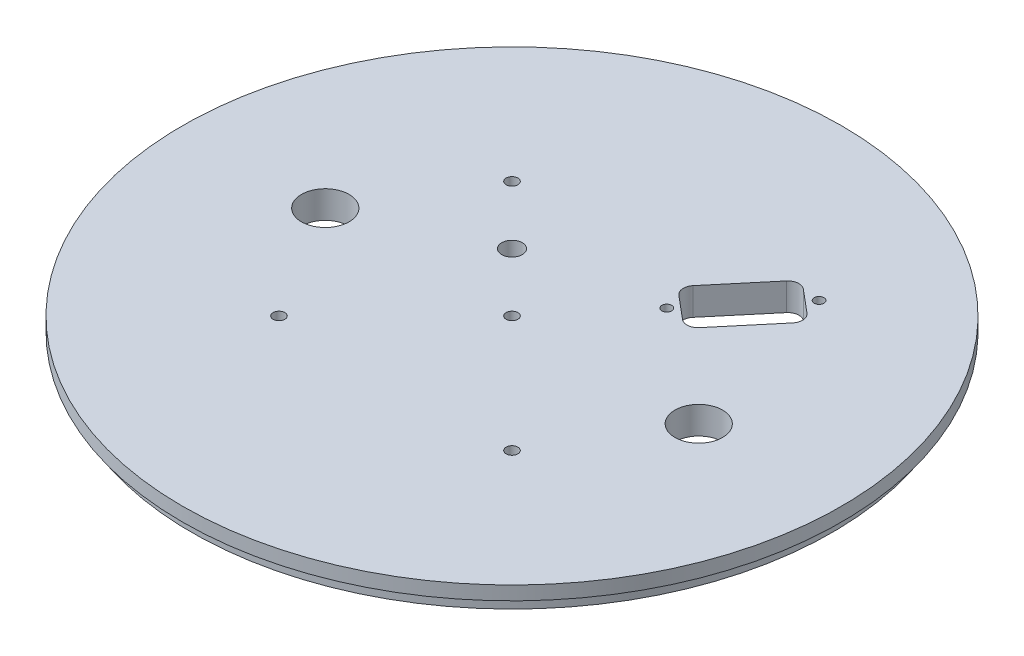
SolidWorks part; units mm, degrees
material "6061-T6 (SS)"
ref_plane "Front Plane" through (0, 0, 0) normal (0, 0, 1) x (1, 0, 0)
ref_plane "Top Plane" through (0, 0, 0) normal (0, 1, 0) x (1, 0, 0)
ref_plane "Right Plane" through (0, 0, 0) normal (1, 0, 0) x (0, 0, -1)
sketch "Sketch1" plane through (0, 0, 0) normal (0, 1, 0) x (1, 0, 0)
  line L0 (0, -76.2) -> (0, 76.2) construction
  line L1 (-76.2, 0) -> (76.2, 0) construction
  line L2 (-26.9408, 26.9408) -> (0, 0) construction
  line L3 (0, 56.7387) -> (0, 29.6936) construction
  line L4 (3.6407, 56.7387) -> (3.6407, 29.6936) construction
  line L5 (-3.6407, 56.7387) -> (-3.6407, 29.6936) construction
  line L6 (0, -56.7387) -> (0, -29.6936) construction
  line L7 (3.6407, -56.7387) -> (3.6407, -29.6936) construction
  line L8 (-3.6407, -56.7387) -> (-3.6407, -29.6936) construction
  line L9 (-53.8815, -53.8815) -> (54.3236, 54.3236) construction
  line L10 (-26.9408, -26.9408) -> (0, 0) construction
  circle A0 centre (0, 0) radius 76.2
  circle A1 centre (0, 0) radius 3.175 construction
  circle A2 centre (43.18, 0) radius 5.5
  circle A3 centre (-43.18, 0) radius 5.5
  circle A4 centre (-26.9408, 26.9408) radius 1.3589
  arc A6 (3.6407, 56.7387) -> (-3.6407, 56.7387) centre (0, 56.7387) ccw construction
  arc A7 (-3.6407, 29.6936) -> (3.6407, 29.6936) centre (0, 29.6936) ccw construction
  arc A8 (3.6407, -56.7387) -> (-3.6407, -56.7387) centre (0, -56.7387) cw construction
  arc A9 (-3.6407, -29.6936) -> (3.6407, -29.6936) centre (0, -29.6936) cw construction
  circle A10 centre (26.9408, -26.9408) radius 1.3589
  circle A11 centre (-13.4704, 13.4704) radius 2.3813
  circle A13 centre (-26.9408, -26.9408) radius 1.3589
  circle A14 centre (0, 0) radius 38.1 construction
  circle A15 centre (0, 0) radius 1.3589
  point P16 (0, 43.2162)
  point P19 (0, 0)
  point P26 (0, -43.2162)
  dimension "D1" = 152.4
  dimension "D2" = 6.35
  dimension "D3" = 11
  dimension "D5" = 2.7178
  dimension "D8" = 4.7625
  dimension "D10" = 2.7178
  dimension "D12" = 2.7178
  dimension "D6" = 38.1
  dimension "D7" = 45
  dimension "D4" = 45
  dimension "D9" = 43.18
  dimension "D11" = 38.1
extrude "Boss-Extrude1" add sketch "Sketch1" along normal blind 6.35
sketch "Sketch2" plane through (0, 0, 0) normal (0, -1, 0) x (1, 0, 0)
  circle A0 centre (0, 0) radius 76.2
  circle A1 centre (0, 0) radius 74.041
  dimension "D1" = 152.4
  dimension "D2" = 148.082
extrude "Cut-Extrude1" cut sketch "Sketch2" against normal blind 3.175
sketch "Sketch3" plane through (0, 6.35, 0) normal (0, 1, 0) x (1, 0, 0)
  line L0 (0, 76.2) -> (0, -76.2) construction
  line L1 (-76.2, 0) -> (76.2, 0) construction
  line L2 (0, 34.798) -> (0, 13.97) construction
  line L3 (3.2385, 34.798) -> (3.2385, 13.97)
  line L4 (-3.2385, 34.798) -> (-3.2385, 13.97)
  line L5 (0, -34.798) -> (0, -13.97) construction
  line L6 (3.2385, -34.798) -> (3.2385, -13.97)
  line L7 (-3.2385, -34.798) -> (-3.2385, -13.97)
  circle A0 centre (0, 0) radius 76.2 construction
  arc A1 (3.2385, 34.798) -> (-3.2385, 34.798) centre (0, 34.798) ccw
  arc A2 (-3.2385, 13.97) -> (3.2385, 13.97) centre (0, 13.97) ccw
  arc A3 (3.2385, -34.798) -> (-3.2385, -34.798) centre (0, -34.798) cw
  arc A4 (-3.2385, -13.97) -> (3.2385, -13.97) centre (0, -13.97) cw
  point P7 (0, 13.97)
  point P8 (0, 34.798)
  point P12 (0, 24.384)
  point P20 (0, -24.384)
  point P25 (0, -34.798)
  point P26 (0, -13.97)
  dimension "D1" = 13.97
  dimension "D2" = 20.828
  dimension "D3" = 6.477
extrude "Cut-Extrude2" cut sketch "Sketch3" against normal blind 3.556 from offset 3.175 offset against normal yes
hole_wizard "Tap Drill for #4-40 Tap1" positions "Sketch5" profile "Sketch6" hole size "#4-40" standard "ANSI Inch" end condition through all
sketch "Sketch5" plane through (0, 6.35, 0) normal (0, 1, 0) x (1, 0, 0)
  line L0 (0, 0) -> (53.6567, 63.9455) construction
  line L2 (0, 0) -> (43.18, 0) construction
  point P0 (16.3268, 19.4575)
  point P2 (32.3965, 38.6086)
  dimension "D1" = 50
  dimension "D2" = 25
  dimension "D3" = 25.4
sketch "Sketch6" plane through (16.3268, 6.35, -19.4575) normal (1, 0, 0) x (0, 0, 1)
  line L0 (0, 0) -> (0, 6.35)
  line L1 (0, 6.35) -> (1.1303, 6.35)
  line L2 (1.1303, 6.35) -> (1.1303, 0)
  line L5 (1.1303, 0) -> (0, 0)
  line L11 (0, -6.35) -> (0, 107.95) construction
  dimension "Thru Hole Dia." = 2.2606
  dimension "Thru Hole Depth" = 6.35
sketch "Sketch4" plane through (0, 6.35, 0) normal (0, 1, 0) x (1, 0, 0)
  line L0 (15.1695, 23.4128) -> (20.423, 19.0046)
  line L1 (14.8564, 26.9913) -> (24.7219, 38.7485)
  line L2 (24.0014, 19.3177) -> (33.8669, 31.0749)
  line L3 (28.3003, 39.0616) -> (33.5538, 34.6533)
  line L4 (0, 0) -> (32.3965, 38.6086) construction
  circle A1 centre (16.3268, 19.4575) radius 1.1303 construction
  arc A2 (24.7219, 38.7485) -> (28.3003, 39.0616) centre (26.6676, 37.1158) cw
  arc A3 (33.8669, 31.0749) -> (33.5538, 34.6533) centre (31.9212, 32.7076) ccw
  arc A4 (20.423, 19.0046) -> (24.0014, 19.3177) centre (22.0557, 20.9503) ccw
  arc A5 (14.8564, 26.9913) -> (15.1695, 23.4128) centre (16.8021, 25.3586) ccw
  point P11 (17.7962, 21.2087)
  dimension "D4" = 2.54
  dimension "D1" = 2.286
  dimension "D2" = 2.286
  dimension "D3" = 11.938
extrude "Cut-Extrude3" cut sketch "Sketch4" against normal through all
equation "\"leadDist\"=1.5"
equation "\"Lead_Screw_Dist\" = 3.4in"
equation "\"D9@Sketch1\"=\"Lead_Screw_Dist\"/2"
equation "\"Lead_Screw_Diam\" = 11mm"
equation "\"D3@Sketch1\"=\"Lead_Screw_Diam\""
equation "\"Bodytube_OD\" = 6.17in"
equation "\"Bodytube_ID\" = 5.998in"
equation "\"Motor_OD\" = 4in"
equation "\"Fwd_Tube_Length\" = 40in"
equation "\"Mid_Tube_Length\" = 1in"
equation "\"Aft_Section_Length\"= 39in"
equation "\"AB_Coupler_OD_Length\"= 1in"
equation "\"AB_Coupling_Section_Length\"= 0.375in"
equation "\"AB_Coupler_Length\"= \"AB_Coupler_OD_Length\" + \"AB_Coupling_Section_Length\" * 2"
equation "\"Cutout_Angle\" = 80"
equation "\"AB_Paddle_Height\" = 0.375in"
equation "\"AB_Coupler_Num_Screws\"= 6"
equation "\"Num_Cutouts\" = 3"
equation "\"AB_Coupler_OD\"= 6.17in"
equation "\"AB_Coupler_ID\"= 5.75in"
equation "\"AB_Coupler_Surface_Diameter\"= 5.998in"
equation "\"AB_Coupling_Screw_Diameter\"= 0.1065in"
equation "\"AB_Central_Bushing_Length\" = .75in"
equation "\"Lead_Screw_Length\" = (\"Mid_Coupler_Length\" + 2*0.375in + 2*0.5in)"
equation "\"Paddle_Pin_Offset\" = .25in"
equation "\"Paddle_Pin_Radius\" = 2.25in"
equation "\"SS_Paddle_Pin_Radius\" = 2.25*0.66in"
equation "\"Paddle_Gear_OD\" = 3.2in"
equation "\"Drive_Gear_OD\" = 1.7in"
equation "\"Fwd_BKHD_From_Top\" = 18in"
equation "\"Fin_Thickness\"= .118in"
equation "\"Guiderail_Cutout_Diameter\"= 1.5in"
equation "\"DB9_Hole_Dist\" = 25mm"
equation "\"Airbrakes_Wire_Hole_Dia\" = .25in"
equation "\"Airbrakes_Wire_Hole_Dist\" = 1.1in"
equation "\"Servo_Gear_Offset\" = 0.5in"
equation "\"Mid_Coupler_Length\" = 13in"
equation "\"D2@Sketch5\"=\"DB9_Hole_Dist\""
equation "\"DB9_Relief_Width\" = 0.47in"
equation "\"DB9_Relief_Hole_Offset\" = 0.09in"
equation "\"D1@Sketch4\"=\"DB9_Relief_Hole_Offset\""
equation "\"D2@Sketch4\"=\"DB9_Relief_Hole_Offset\""
equation "\"D3@Sketch4\"=\"DB9_Relief_Width\""
